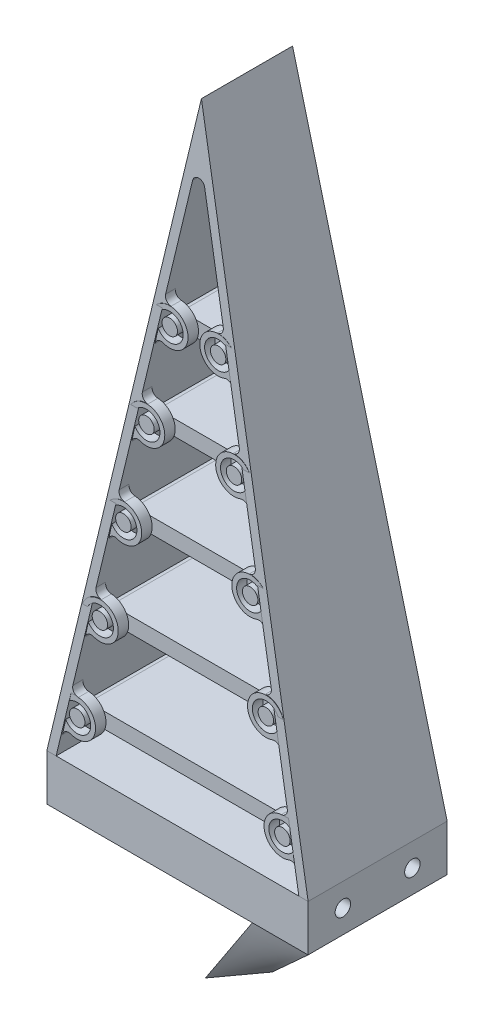
SolidWorks part; units mm, degrees
ref_plane "Ebene vorne" through (0, 0, 0) normal (0, 0, 1) x (1, 0, 0)
ref_plane "Ebene oben" through (0, 0, 0) normal (0, 1, 0) x (1, 0, 0)
ref_plane "Ebene rechts" through (0, 0, 0) normal (1, 0, 0) x (0, 0, -1)
ref_plane "Ebene7" through (0, 0, 9) normal (0, 0, 1) x (1, 0, 0)
ref_plane "Ebene8" through (17, 0, 0) normal (1, 0, 0) x (0, 0, -1)
sketch "Skizze1" plane through (0, 0, 0) normal (0, 0, 1) x (1, 0, 0)
  line L0 (0, 0) -> (16.9111, -80)
  line L1 (16.9111, -80) -> (15.7111, -80)
  line L2 (15.7111, -80) -> (0, -5.6767)
  line L3 (0, -5.6767) -> (-15.7111, -80)
  line L4 (-15.7111, -80) -> (-16.9111, -80)
  line L5 (-16.9111, -80) -> (0, 0)
  point P2 (-16.3111, -80)
  dimension "D1" = 1.2
  dimension "D2" = 1.2
  dimension "D3" = 23.872
  dimension "D4" = 80
extrude "Aufsatz-Linear austragen4" add sketch "Skizze1" along normal blind 18
sketch "Skizze11" plane through (17, 0, 0) normal (1, 0, 0) x (0, 0, -1)
  line L0 (-18, -80) -> (-14.9, 0)
  line L1 (-18, 0) -> (0, 0) construction
  line L2 (-14.9, 0) -> (-18, 0)
  line L3 (-18, 0) -> (-18, -80)
  line L4 (0, -80) -> (-3.1, 0)
  line L5 (-3.1, 0) -> (0, 0)
  line L6 (0, 0) -> (0, -80)
  dimension "D1" = 3.1
  dimension "D2" = 3.1
extrude "Schnitt-Linear austragen1" cut sketch "Skizze11" against normal through all
sketch "Skizze6" plane through (0, 0, 9) normal (0, 0, 1) x (1, 0, 0)
  line L1 (0, -5.6767) -> (-15.7111, -80) construction
  line L2 (15.7111, -80) -> (0, -5.6767) construction
  line L8 (3.1325, -25.6767) -> (-3.1325, -25.6767)
  line L11 (-3.1325, -27.6767) -> (3.1325, -27.6767)
  arc A0 (-3.1325, -25.6767) -> (-3.1325, -27.6767) centre (-3.1325, -26.6767) ccw
  arc A1 (3.1325, -25.6767) -> (3.1325, -27.6767) centre (3.1325, -26.6767) cw
  point P4 (-4.1325, -26.6767)
  point P9 (4.1325, -26.6767)
  dimension "D3" = 0.3
  dimension "D1" = 20
  dimension "D2" = 2
  dimension "D4" = 0.3
extrude "Aufsatz-Linear austragen5" add sketch "Skizze6" along normal blind 5.37 and the other way blind 5.37
sketch "Skizze7" plane through (0, 0, 9) normal (0, 0, 1) x (1, 0, 0)
  line L9 (5.6692, -37.6767) -> (-5.6692, -37.6767)
  line L12 (-5.6692, -39.6767) -> (5.6692, -39.6767)
  line L13 (-3.1325, -27.6767) -> (3.1325, -27.6767) construction
  line L14 (0, -5.6767) -> (-15.7111, -80) construction
  line L15 (15.7111, -80) -> (0, -5.6767) construction
  arc A0 (-5.6692, -37.6767) -> (-5.6692, -39.6767) centre (-5.6692, -38.6767) ccw
  arc A1 (5.6692, -37.6767) -> (5.6692, -39.6767) centre (5.6692, -38.6767) cw
  point P3 (-6.6692, -38.6767)
  point P10 (6.6692, -38.6767)
  dimension "D3" = 0.3
  dimension "D1" = 10
  dimension "D2" = 2
  dimension "D4" = 0.3
extrude "Aufsatz-Linear austragen6" add sketch "Skizze7" along normal blind 5.85 and the other way blind 5.85
sketch "Skizze8" plane through (0, 0, 9) normal (0, 0, 1) x (1, 0, 0)
  line L9 (8.2059, -49.6767) -> (-8.2059, -49.6767)
  line L12 (-8.2059, -51.6767) -> (8.2059, -51.6767)
  line L13 (-5.6692, -39.6767) -> (5.6692, -39.6767) construction
  line L14 (0, -5.6767) -> (-15.7111, -80) construction
  line L15 (15.7111, -80) -> (0, -5.6767) construction
  arc A0 (-8.2059, -49.6767) -> (-8.2059, -51.6767) centre (-8.2059, -50.6767) ccw
  arc A1 (8.2059, -49.6767) -> (8.2059, -51.6767) centre (8.2059, -50.6767) cw
  point P6 (-9.2059, -50.6767)
  point P11 (9.2059, -50.6767)
  dimension "D3" = 0.3
  dimension "D1" = 10
  dimension "D2" = 2
  dimension "D4" = 0.3
extrude "Aufsatz-Linear austragen7" add sketch "Skizze8" along normal blind 6.3 and the other way blind 6.3
sketch "Skizze9" plane through (0, 0, 9) normal (0, 0, 1) x (1, 0, 0)
  line L9 (10.7426, -61.6767) -> (-10.7426, -61.6767)
  line L12 (-10.7426, -63.6767) -> (10.7426, -63.6767)
  line L13 (-8.2059, -51.6767) -> (8.2059, -51.6767) construction
  line L14 (0, -5.6767) -> (-15.7111, -80) construction
  line L15 (15.7111, -80) -> (0, -5.6767) construction
  arc A0 (-10.7426, -61.6767) -> (-10.7426, -63.6767) centre (-10.7426, -62.6767) ccw
  arc A1 (10.7426, -61.6767) -> (10.7426, -63.6767) centre (10.7426, -62.6767) cw
  point P3 (-11.7426, -62.6767)
  point P10 (11.7426, -62.6767)
  dimension "D3" = 0.3
  dimension "D1" = 10
  dimension "D2" = 2
  dimension "D4" = 0.3
extrude "Aufsatz-Linear austragen8" add sketch "Skizze9" along normal blind 6.8 and the other way blind 6.8
sketch "Skizze10" plane through (0, 0, 9) normal (0, 0, 1) x (1, 0, 0)
  line L9 (13.2792, -73.6767) -> (-13.2792, -73.6767)
  line L12 (-13.2792, -75.6767) -> (13.2792, -75.6767)
  line L13 (-10.7426, -63.6767) -> (10.7426, -63.6767) construction
  line L14 (0, -5.6767) -> (-15.7111, -80) construction
  line L15 (15.7111, -80) -> (0, -5.6767) construction
  arc A0 (-13.2792, -73.6767) -> (-13.2792, -75.6767) centre (-13.2792, -74.6767) ccw
  arc A1 (13.2792, -73.6767) -> (13.2792, -75.6767) centre (13.2792, -74.6767) cw
  point P3 (-14.2792, -74.6767)
  point P10 (14.2792, -74.6767)
  dimension "D3" = 0.3
  dimension "D1" = 10
  dimension "D2" = 2
  dimension "D4" = 0.3
extrude "Aufsatz-Linear austragen9" add sketch "Skizze10" along normal blind 7.2 and the other way blind 7.2
sketch "Skizze13" plane through (0, 0, 14.37) normal (0, 0, 1) x (1, 0, 0)
  circle A0 centre (-3.1325, -26.6767) radius 1
  circle A1 centre (3.1325, -26.6767) radius 1
  dimension "D1" = 2
  dimension "D2" = 2
extrude "Aufsatz-Linear austragen12" add sketch "Skizze13" along normal blind 1.5
sketch "Skizze15" plane through (0, 0, 15.3) normal (0, 0, 1) x (1, 0, 0)
  circle A0 centre (-8.2059, -50.6767) radius 1
  circle A1 centre (8.2059, -50.6767) radius 1
extrude "Aufsatz-Linear austragen14" add sketch "Skizze15" along normal blind 1.5
sketch "Skizze14" plane through (0, 0, 14.85) normal (0, 0, 1) x (1, 0, 0)
  circle A0 centre (-5.6692, -38.6767) radius 1
  circle A1 centre (5.6692, -38.6767) radius 1
extrude "Aufsatz-Linear austragen13" add sketch "Skizze14" along normal blind 1.5
sketch "Skizze16" plane through (0, 0, 15.8) normal (0, 0, 1) x (1, 0, 0)
  circle A0 centre (-10.7426, -62.6767) radius 1
  circle A1 centre (10.7426, -62.6767) radius 1
extrude "Aufsatz-Linear austragen15" add sketch "Skizze16" along normal blind 1.5
sketch "Skizze17" plane through (0, 0, 16.2) normal (0, 0, 1) x (1, 0, 0)
  circle A0 centre (-13.2792, -74.6767) radius 1
  circle A1 centre (13.2792, -74.6767) radius 1
extrude "Aufsatz-Linear austragen16" add sketch "Skizze17" along normal blind 1.5
sketch "Skizze18" plane through (0, 0, 3.63) normal (0, 0, -1) x (-1, 0, 0)
  circle A0 centre (-3.1325, -26.6767) radius 1
  circle A1 centre (3.1325, -26.6767) radius 1
extrude "Aufsatz-Linear austragen17" add sketch "Skizze18" along normal blind 1.5
sketch "Skizze19" plane through (0, 0, 3.15) normal (0, 0, -1) x (-1, 0, 0)
  circle A0 centre (-5.6692, -38.6767) radius 1
  circle A1 centre (5.6692, -38.6767) radius 1
extrude "Aufsatz-Linear austragen18" add sketch "Skizze19" along normal blind 1.5
sketch "Skizze20" plane through (0, 0, 2.7) normal (0, 0, -1) x (-1, 0, 0)
  circle A0 centre (-8.2059, -50.6767) radius 1
  circle A1 centre (8.2059, -50.6767) radius 1
extrude "Aufsatz-Linear austragen19" add sketch "Skizze20" along normal blind 1.5
sketch "Skizze21" plane through (0, 0, 2.2) normal (0, 0, -1) x (-1, 0, 0)
  circle A0 centre (-10.7426, -62.6767) radius 1
  circle A1 centre (10.7426, -62.6767) radius 1
extrude "Aufsatz-Linear austragen20" add sketch "Skizze21" along normal blind 1.5
sketch "Skizze22" plane through (0, 0, 1.8) normal (0, 0, -1) x (-1, 0, 0)
  circle A0 centre (-13.2792, -74.6767) radius 1
  circle A1 centre (13.2792, -74.6767) radius 1
extrude "Aufsatz-Linear austragen21" add sketch "Skizze22" along normal blind 1.5
sketch "Skizze24" plane through (0, 0, 15.87) normal (0, 0, 1) x (1, 0, 0)
  circle A0 centre (-3.1325, -26.6767) radius 1.75
  circle A1 centre (-3.1325, -26.6767) radius 2.375
  circle A2 centre (3.1325, -26.6767) radius 1.75
  circle A3 centre (3.1325, -26.6767) radius 2.375
  dimension "D1" = 3.5
  dimension "D2" = 4.75
  dimension "D3" = 3.5
  dimension "D4" = 4.75
extrude "Aufsatz-Linear austragen22" add sketch "Skizze24" against normal blind 1.35
sketch "Skizze25" plane through (0, 0, 16.35) normal (0, 0, 1) x (1, 0, 0)
  circle A0 centre (-5.6692, -38.6767) radius 1.75
  circle A1 centre (-5.6692, -38.6767) radius 2.375
  circle A2 centre (5.6692, -38.6767) radius 1.75
  circle A3 centre (5.6692, -38.6767) radius 2.375
  dimension "D1" = 3.5
  dimension "D2" = 4.75
  dimension "D3" = 3.5
  dimension "D4" = 4.75
extrude "Aufsatz-Linear austragen23" add sketch "Skizze25" against normal blind 1.35
sketch "Skizze26" plane through (0, 0, 16.8) normal (0, 0, 1) x (1, 0, 0)
  circle A0 centre (-8.2059, -50.6767) radius 1.75
  circle A1 centre (-8.2059, -50.6767) radius 2.375
  circle A2 centre (8.2059, -50.6767) radius 1.75
  circle A3 centre (8.2059, -50.6767) radius 2.375
  dimension "D1" = 3.5
  dimension "D2" = 4.75
  dimension "D3" = 3.5
  dimension "D4" = 4.75
extrude "Aufsatz-Linear austragen24" add sketch "Skizze26" against normal blind 1.35
sketch "Skizze27" plane through (0, 0, 17.3) normal (0, 0, 1) x (1, 0, 0)
  circle A0 centre (-10.7426, -62.6767) radius 1.75
  circle A1 centre (-10.7426, -62.6767) radius 2.375
  circle A2 centre (10.7426, -62.6767) radius 1.75
  circle A3 centre (10.7426, -62.6767) radius 2.375
  dimension "D1" = 3.5
  dimension "D2" = 4.75
  dimension "D3" = 3.5
  dimension "D4" = 4.75
extrude "Aufsatz-Linear austragen25" add sketch "Skizze27" against normal blind 1.35
sketch "Skizze28" plane through (0, 0, 17.7) normal (0, 0, 1) x (1, 0, 0)
  circle A0 centre (-13.2792, -74.6767) radius 1.75
  circle A1 centre (-13.2792, -74.6767) radius 2.375
  circle A2 centre (13.2792, -74.6767) radius 1.75
  circle A3 centre (13.2792, -74.6767) radius 2.375
  dimension "D1" = 3.5
  dimension "D2" = 4.75
  dimension "D3" = 3.5
  dimension "D4" = 4.75
extrude "Aufsatz-Linear austragen26" add sketch "Skizze28" against normal blind 1.35
sketch "Skizze29" plane through (0, 0, 2.13) normal (0, 0, -1) x (-1, 0, 0)
  circle A0 centre (-3.1325, -26.6767) radius 1.75
  circle A1 centre (-3.1325, -26.6767) radius 2.375
  circle A2 centre (3.1325, -26.6767) radius 1.75
  circle A3 centre (3.1325, -26.6767) radius 2.375
extrude "Aufsatz-Linear austragen27" add sketch "Skizze29" against normal blind 1.35
sketch "Skizze30" plane through (0, 0, 1.65) normal (0, 0, -1) x (-1, 0, 0)
  circle A0 centre (-5.6692, -38.6767) radius 1.75
  circle A1 centre (-5.6692, -38.6767) radius 2.375
  circle A2 centre (5.6692, -38.6767) radius 1.75
  circle A3 centre (5.6692, -38.6767) radius 2.375
extrude "Aufsatz-Linear austragen28" add sketch "Skizze30" against normal blind 1.35
sketch "Skizze31" plane through (0, 0, 1.2) normal (0, 0, -1) x (-1, 0, 0)
  circle A0 centre (-8.2059, -50.6767) radius 1.75
  circle A1 centre (-8.2059, -50.6767) radius 2.375
  circle A2 centre (8.2059, -50.6767) radius 1.75
  circle A3 centre (8.2059, -50.6767) radius 2.375
extrude "Aufsatz-Linear austragen29" add sketch "Skizze31" against normal blind 1.35
sketch "Skizze32" plane through (0, 0, 0.7) normal (0, 0, -1) x (-1, 0, 0)
  circle A0 centre (-10.7426, -62.6767) radius 1.75
  circle A1 centre (-10.7426, -62.6767) radius 2.375
  circle A2 centre (10.7426, -62.6767) radius 1.75
  circle A3 centre (10.7426, -62.6767) radius 2.375
extrude "Aufsatz-Linear austragen30" add sketch "Skizze32" against normal blind 1.35
sketch "Skizze33" plane through (0, 0, 0.3) normal (0, 0, -1) x (-1, 0, 0)
  circle A0 centre (-13.2792, -74.6767) radius 1.75
  circle A1 centre (-13.2792, -74.6767) radius 2.375
  circle A2 centre (13.2792, -74.6767) radius 1.75
  circle A3 centre (13.2792, -74.6767) radius 2.375
extrude "Aufsatz-Linear austragen31" add sketch "Skizze33" against normal blind 1.35
fillet "Verrundung1" radius 0.8 1 edges at (0, -5.6767, 9)
fillet "Verrundung2" radius 0.8 40 edges at (12.4073, -64.3707, 16.625) (9.8706, -52.3707, 16.125) (7.3339, -40.3707, 15.675) (4.7973, -28.3707, 15.195) (-4.7973, -28.3707, 15.195) (-7.3339, -40.3707, 15.675) (-9.8706, -52.3707, 16.125) (-12.4073, -64.3707, 16.625) (-14.9439, -76.3707, 17.025) (14.9439, -76.3707, 17.025) (14.116, -72.454, 17.025) (-14.116, -72.454, 17.025) (-11.5793, -60.454, 16.5963) (11.5793, -60.454, 16.5963) (9.0427, -48.454, 16.1138) (-9.0427, -48.454, 16.1138) (-6.506, -36.454, 15.6563) (6.506, -36.454, 15.6563) (3.9693, -24.454, 15.1838) (-3.9693, -24.454, 15.1838) (-7.3339, -40.3707, 2.325) (-4.7973, -28.3707, 2.805) (-3.9693, -24.454, 2.8162) (-6.506, -36.454, 2.3437) (-9.0427, -48.454, 1.8862) (-9.8706, -52.3707, 1.875) (-12.4073, -64.3707, 1.375) (-11.5793, -60.454, 1.4037) (-14.116, -72.454, 0.975) (-14.9439, -76.3707, 0.975) (14.9439, -76.3707, 0.975) (14.116, -72.454, 0.975) (12.4073, -64.3707, 1.375) (11.5793, -60.454, 1.4037) (9.8706, -52.3707, 1.875) (9.0427, -48.454, 1.8862) (7.3339, -40.3707, 2.325) (6.506, -36.454, 2.3437) (4.7973, -28.3707, 2.805) (3.9693, -24.454, 2.8162)
sketch "Skizze37" plane through (0, -80, 0) normal (0, -1, 0) x (1, 0, 0)
  line L0 (-16.9111, 0) -> (-15.7111, 0)
  line L1 (-15.7111, 0) -> (16.9111, 0)
  line L2 (16.9111, 0) -> (16.9111, 18)
  line L3 (16.9111, 18) -> (-16.9111, 18)
  line L4 (-16.9111, 18) -> (-16.9111, 0)
extrude "Aufsatz-Linear austragen32" add sketch "Skizze37" along normal blind 6
ref_plane "Ebene9" through (0, 0, 9) normal (0, 0, 1) x (1, 0, 0)
ref_plane "Ebene15" through (41.4669, -71.8227, 0) normal (0.5, -0.866, 0) x (0, 0, 1)
sketch "Skizze68" plane through (0, -86, 0) normal (0, -1, 0) x (1, 0, 0)
  line L0 (16.9111, 0) -> (16.9111, 18)
  line L1 (-16.9111, 0) -> (16.9111, 0) construction
  line L2 (16.9111, 18) -> (-16.9111, 18) construction
  line L3 (16.9111, 18) -> (9.6937, 18)
  line L4 (9.6937, 18) -> (9.6937, 0)
  line L5 (9.6937, 0) -> (16.9111, 0)
  line L6 (16.9111, 0) -> (16.9111, 18) construction
  dimension "D1" = 7.2174
sketch "Skizze69" plane through (41.4669, -71.8227, 0) normal (0.5, -0.866, 0) x (0, 0, 1)
  line L0 (4, 54.7108) -> (4, 44.7108)
  line L1 (14, 44.7108) -> (14, 54.7108)
  line L2 (14, 54.7108) -> (4, 54.7108)
  line L3 (4, 44.7108) -> (14, 44.7108)
  line L4 (9, -1.1) -> (9, 1.1) construction
  point P0 (9, 44.7108)
sketch "Skizze79" plane through (0, -86, 0) normal (0, -1, 0) x (1, 0, 0)
  line L0 (-16.9111, 0) -> (22.5311, 0) construction
  line L1 (-16.9111, 18) -> (22.5311, 18) construction
  dimension "D1" = 5.62
  dimension "D2" = 5.62
ref_plane "Ebene16" through (42.8719, -74.2563, 0) normal (0.5, -0.866, 0) x (0, 0, -1)
sketch "Skizze80" plane through (42.8719, -74.2563, 0) normal (0.5, -0.866, 0) x (0, 0, -1)
  line L0 (-4, -49.9329) -> (-4, -39.9511)
  line L1 (-4, -39.9511) -> (-14.009, -39.9511)
  line L2 (-14.009, -39.9511) -> (-14.009, -49.9329)
  line L3 (-14.009, -49.9329) -> (-4, -49.9329)
  point P2 (-14.009, -49.9329)
loft "Ausformung1" add profiles "Skizze68", "Skizze80"
sketch "Skizze78" plane through (0, -86, 0) normal (0, -1, 0) x (1, 0, 0)
  line L0 (1.1, 9) -> (-1.1, 9) construction
  circle A0 centre (-13.6144, 9) radius 0.5
extrude "Schnitt-Linear austragen6" cut sketch "Skizze78" against normal up to next (6 mm away) contours A0
sketch "Skizze83" plane through (42.8719, -74.2563, 0) normal (0.5, -0.866, 0) x (0.866, 0.5, 0)
  circle A0 centre (-44.942, 9.0045) radius 1
  dimension "D1" = 2
extrude "Schnitt-Linear austragen7" cut sketch "Skizze83" against normal blind 4
sketch "Skizze84" plane through (-16.9111, 0, 0) normal (-1, 0, 0) x (0, 0, 1)
  line L0 (18, -83) -> (0, -83) construction
  line L1 (18, -86) -> (18, -80) construction
  line L2 (0, -86) -> (0, -80) construction
  line L3 (9, -86) -> (9, -80) construction
  line L4 (18, -86) -> (0, -86) construction
  line L5 (18, -80) -> (0, -80) construction
  circle A0 centre (13.5, -83) radius 2
  circle A1 centre (4.5, -83) radius 2
  dimension "D1" = 4
  dimension "D2" = 4
  dimension "D3" = 4.5
  dimension "D4" = 4.5
extrude "Schnitt-Linear austragen8" cut sketch "Skizze84" against normal blind 32
sketch "Skizze86" plane through (16.9111, 0, 0) normal (1, 0, 0) x (0, 0, -1)
  line L0 (0, -83) -> (-18, -83) construction
  line L1 (0, -86) -> (0, -80) construction
  line L2 (-18, -86) -> (-18, -80) construction
  line L3 (-9, -86) -> (-9, -80) construction
  line L4 (0, -86) -> (-18, -86) construction
  line L5 (-18, -80) -> (0, -80) construction
  circle A0 centre (-13.5, -83) radius 1
  circle A1 centre (-4.5, -83) radius 1
  dimension "D1" = 2
  dimension "D2" = 2
  dimension "D3" = 4.5
  dimension "D4" = 4.5
extrude "Schnitt-Linear austragen9" cut sketch "Skizze86" against normal blind 4
